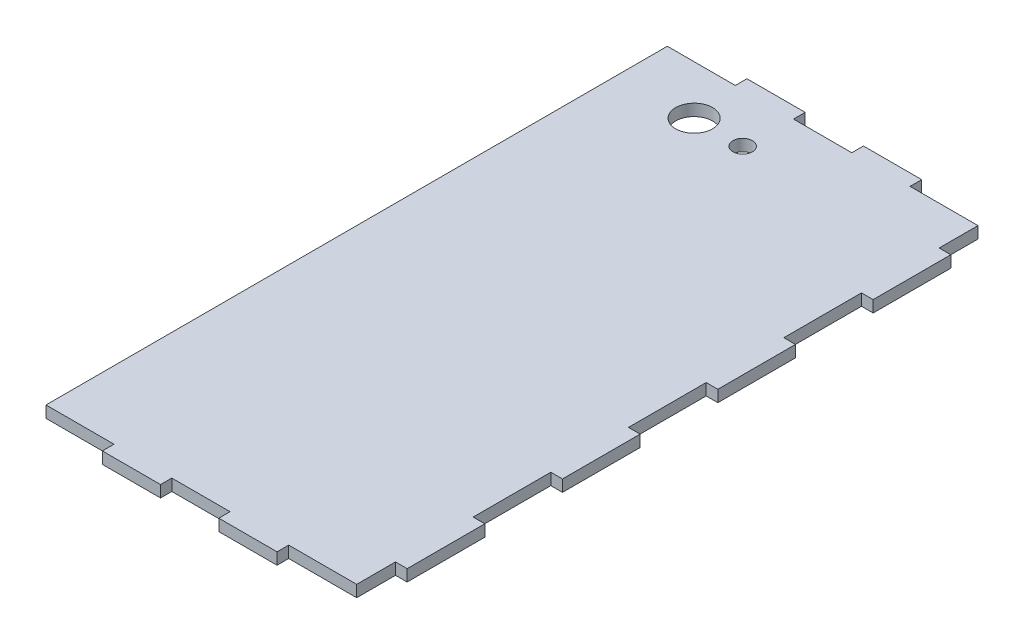
SolidWorks part; units mm, degrees
ref_plane "Alzado" through (0, 0, 0) normal (0, 0, 1) x (1, 0, 0)
ref_plane "Planta" through (0, 0, 0) normal (0, 1, 0) x (1, 0, 0)
ref_plane "Vista lateral" through (0, 0, 0) normal (1, 0, 0) x (0, 0, -1)
sketch "Croquis1" plane through (0, 0, 0) normal (0, 1, 0) x (1, 0, 0)
  line L0 (23, 3) -> (38, 3)
  line L1 (88.5, 16) -> (88.5, 36)
  line L2 (85.5, 166) -> (68, 166)
  line L3 (37.5, 153.3969) -> (37.5, 5.8969) construction
  line L4 (5.5, 153) -> (5.5, 13)
  line L5 (5.5, 73) -> (5.5, 93)
  line L6 (5.5, 166) -> (23, 166)
  line L7 (23, 166) -> (23, 169)
  line L8 (23, 169) -> (38, 169)
  line L9 (5.5, 113) -> (5.5, 133)
  line L10 (38, 169) -> (38, 166)
  line L11 (38, 166) -> (45.5, 166)
  line L12 (23, 166) -> (5.5, 166)
  line L13 (53, 169) -> (53, 166)
  line L14 (68, 169) -> (53, 169)
  line L15 (5.5, 53) -> (5.5, 33)
  line L16 (68, 166) -> (68, 169)
  line L17 (53, 166) -> (38, 166)
  line L18 (5.5, 153) -> (5.5, 166)
  line L19 (5.5, 13) -> (5.5, 6)
  line L20 (85.5, 156) -> (85.5, 153.3969)
  line L21 (53, 5.8969) -> (38, 5.8969)
  line L22 (38, 5.8969) -> (38, 3)
  line L23 (38, 3) -> (23, 3)
  line L24 (23, 3) -> (23, 6)
  line L25 (23, 6) -> (5.5, 6)
  line L26 (68, 6) -> (85.5, 6)
  line L27 (68, 3) -> (68, 6)
  line L28 (53, 5.8969) -> (53, 3)
  line L29 (85.5, 16) -> (85.5, 6)
  line L30 (85.5, 156) -> (85.5, 166)
  line L31 (85.5, 76) -> (88.5, 76)
  line L32 (88.5, 56) -> (85.5, 56)
  line L33 (85.5, 56) -> (85.5, 36)
  line L34 (85.5, 36) -> (88.5, 36)
  line L35 (88.5, 16) -> (85.5, 16)
  line L36 (88.5, 156) -> (85.5, 156)
  line L37 (85.5, 136) -> (88.5, 136)
  line L38 (85.5, 116) -> (85.5, 136)
  line L39 (88.5, 116) -> (85.5, 116)
  line L40 (85.5, 96) -> (88.5, 96)
  line L41 (85.5, 76) -> (85.5, 96)
  line L42 (88.5, 136) -> (88.5, 156)
  line L43 (53, 3) -> (68, 3)
  line L44 (88.5, 56) -> (88.5, 76)
  line L45 (88.5, 96) -> (88.5, 116)
  line L46 (85.5, 153.3969) -> (37.5, 153.3969) construction
  line L47 (37.5, 153.3969) -> (25, 153.3969)
  circle A0 centre (37.5, 153.3969) radius 2.5
  circle A1 centre (25, 153.3969) radius 4.75
  dimension "D4" = 5
  dimension "D18" = 9.5
  dimension "D2" = 80
  dimension "D3" = 80
  dimension "D5" = 3
  dimension "D6" = 20
  dimension "D7" = 3
  dimension "D8" = 147.5
  dimension "D9" = 3
  dimension "D10" = 15
  dimension "D11" = 17.5
  dimension "D12" = 160
  dimension "D13" = 15
  dimension "D14" = 10
  dimension "D15" = 10
  dimension "D16" = 48
  dimension "D17" = 12.5
extrude "Saliente-Extruir1" add sketch "Croquis1" along normal blind 3 contours L15 L19 L25 L24 L0 L22 L21 L28 L43 L27 L26 L29 L35 L1 L34 L33 L32 L44 L31 L41 L40 L45 L39 L38 L37 L42 L36 L30 L2 L18 L9 L5 A0 region at (46.3811, 0, -85.526)
